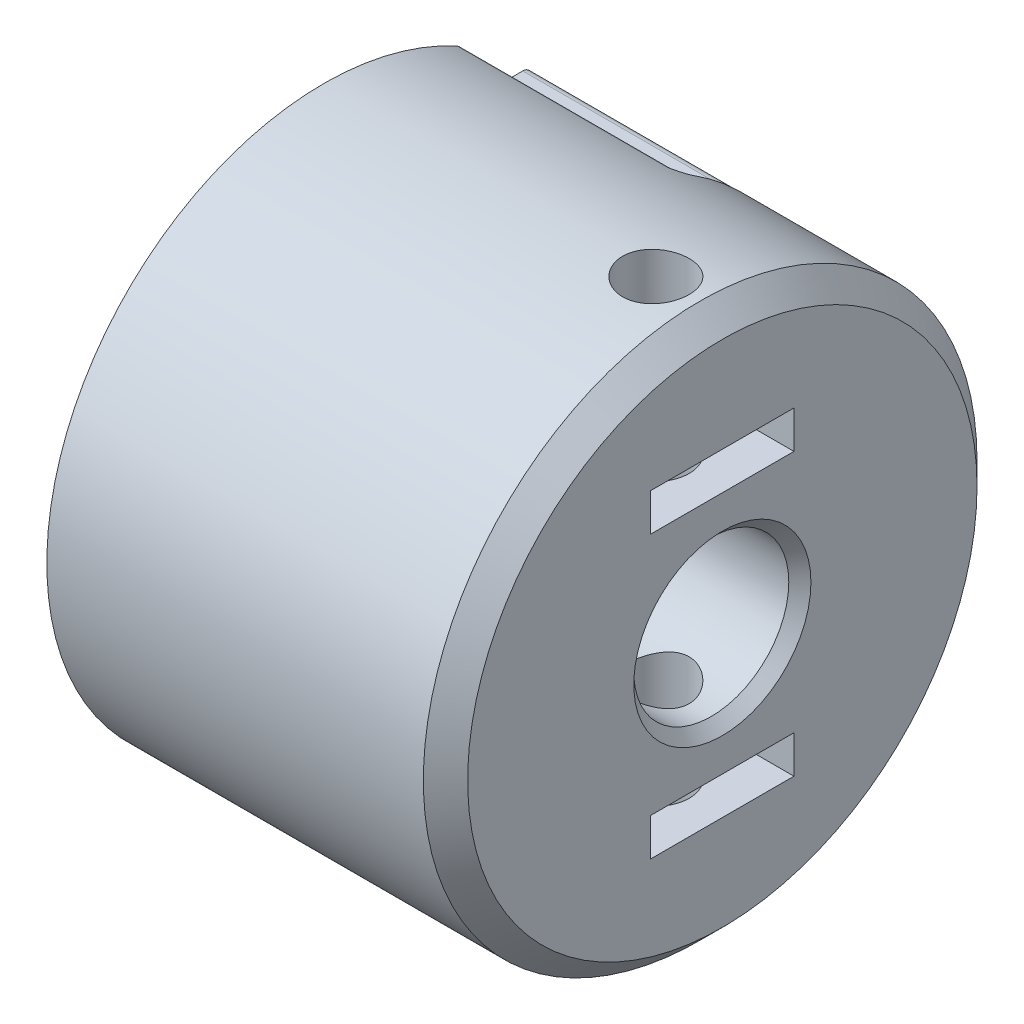
SolidWorks part; units mm, degrees
ref_plane "Front Plane" through (0, 0, 0) normal (0, 0, 1) x (1, 0, 0)
ref_plane "Top Plane" through (0, 0, 0) normal (0, 1, 0) x (1, 0, 0)
ref_plane "Right Plane" through (0, 0, 0) normal (1, 0, 0) x (0, 0, -1)
ref_axis "Axis1" through (88.99, 0, 0) along (-1, 0, 0)
sketch "Sketch1" plane through (0, 0, 0) normal (0, 0, 1) x (1, 0, 0)
  line L0 (-12, 12.5) -> (0, 12.5)
  line L3 (6, 10) -> (6, 3)
  line L4 (6, 3) -> (-2, 3)
  line L5 (-2, 3) -> (-2, 10.2)
  line L6 (88.99, 0) -> (-88.99, 0) construction
  line L7 (-2, 10.2) -> (-12, 10.2)
  line L8 (-12, 10.2) -> (-12, 12.5)
  line L9 (6, 10) -> (6, 12.5)
  line L10 (6, 12.5) -> (0, 12.5)
  dimension "D1" = 3
  dimension "D4" = 12.5
  dimension "D5" = 10.2
  dimension "D6" = 10
revolve "Revolve1" add sketch "Sketch1" angle 360 about axis through (88.99, 0, 0) along (-1, 0, 0)
sketch "Sketch2" plane through (0, 0, 0) normal (0, 1, 0) x (1, 0, 0)
  line L0 (88.99, 0) -> (-88.99, 0) construction
  line L1 (0, 0) -> (6, 0) construction
  circle A0 centre (3, 0) radius 1.5
  dimension "D1" = 3
extrude "Cut-Extrude1" cut sketch "Sketch2" along normal through all both and the other way through all
sketch "Sketch3" plane through (-2, 0, 0) normal (-1, 0, 0) x (0, 0, 1)
  line L1 (0, 10.2) -> (-9.1652, 10.2)
  line L2 (0, 10.2) -> (0, 8.5)
  line L3 (0, 8.5) -> (-9.1652, 8.5)
  line L4 (-9.1652, 10.2) -> (-9.1652, 8.5)
  circle A0 centre (0, 0) radius 10.2 construction
  circle A1 centre (0, 0) radius 10.2 construction
  circle A2 centre (0, 0) radius 12.5 construction
  dimension "D1" = 1.7
extrude "Cut-Extrude2" cut sketch "Sketch3" along normal through all
fillet "Fillet1" radius 0.4 3 edges at (-7, 8.5, -5.6383) (-7, 8.5, -9.1652) (-7, 10.2, -7.2256)
sketch "Sketch4" plane through (-2, 0, 0) normal (-1, 0, 0) x (0, 0, 1)
  circle A0 centre (0, 0) radius 3
  circle A1 centre (0, 0) radius 6.5
  circle A2 centre (0, 0) radius 3 construction
  dimension "D1" = 13
extrude "Boss-Extrude1" add sketch "Sketch4" along normal blind 19.2405
chamfer "Chamfer1" distance 1.5 angle 45 2 edges at (-21.2405, 0, 3) (-21.2405, 0, 6.5)
chamfer "Chamfer2" distance 0.5 angle 45 1 edges at (6, 0, -3)
fillet "Fillet2" radius 0.5 7 edges at (-2, 10.5004, -6.2226) (-2, 10.2, -2.9176) (-2, 8.4655, -9.1515) (-2, 8.5, -7.9131) (-2, 8.2374, -6.4617) (-2, 0, 6.5) (-2, -9.5797, 3.5027)
sketch "Sketch5" plane through (-21.2405, 0, 0) normal (-1, 0, 0) x (0, 0, 1)
  circle A0 centre (0, 0) radius 7.9634
extrude "Cut-Extrude3" cut sketch "Sketch5" against normal up to surface (19.2405 mm away) up to face at (-2, 0, 7)
sketch "Sketch6" plane through (6, 0, 0) normal (1, 0, 0) x (0, 0, -1)
  circle A0 centre (0, 0) radius 3.5
  circle A1 centre (0, 0) radius 3 construction
  dimension "D1" = 0.5
extrude "Cut-Extrude4" cut sketch "Sketch6" against normal blind 10
chamfer "Chamfer3" distance 0.5 angle 45 1 edges at (6, 0, -3.5)
sketch "Sketch7" plane through (-12, 0, 0) normal (-1, 0, 0) x (0, 0, 1)
  circle A0 centre (0, 0) radius 10.7
  arc A1 (-6.5794, 7.7943) -> (0, 10.2) centre (0, 0) ccw construction
  dimension "D1" = 0.5
extrude "Cut-Extrude5" cut sketch "Sketch7" against normal blind 10
ref_axis "Axis2" through (3, -2.7397, 0) along (0, -1, 0)
sketch "Sketch8" plane through (0, 0, 0) normal (0, 1, 0) x (1, 0, 0)
  line L5 (0.2, 1.6166) -> (0.2, -1.6166)
  line L10 (5.5, 0) -> (7.7963, 0) construction
  line L15 (0.2, -1.6166) -> (0.2, -2.4249)
  line L16 (8.377, 0) -> (8.6897, 0) construction
  line L22 (4.3186, 3.2332) -> (8.377, 3.2332)
  line L24 (4.3186, -3.2332) -> (8.377, -3.2332)
  line L25 (8.377, 3.2332) -> (8.377, -3.2332)
  line L26 (3, 3.2332) -> (4.3186, 3.2332)
  line L28 (4.3186, -3.2332) -> (3, -3.2332)
  line L29 (0.2, -2.4249) -> (3, -3.2332)
  line L31 (0.2, 1.6166) -> (0.2, 2.4249)
  line L32 (0.2, 2.4249) -> (3, 3.2332)
extrude "Cut-Extrude6" cut sketch "Sketch8" along normal blind 1.7 from offset 5.5
chamfer "Chamfer5" distance 1 angle 45 1 edges at (6, 0, -12.5)
mirror "Mirror1" about plane through (0, 0, 0) normal (0, 1, 0) of "Cut-Extrude6"
